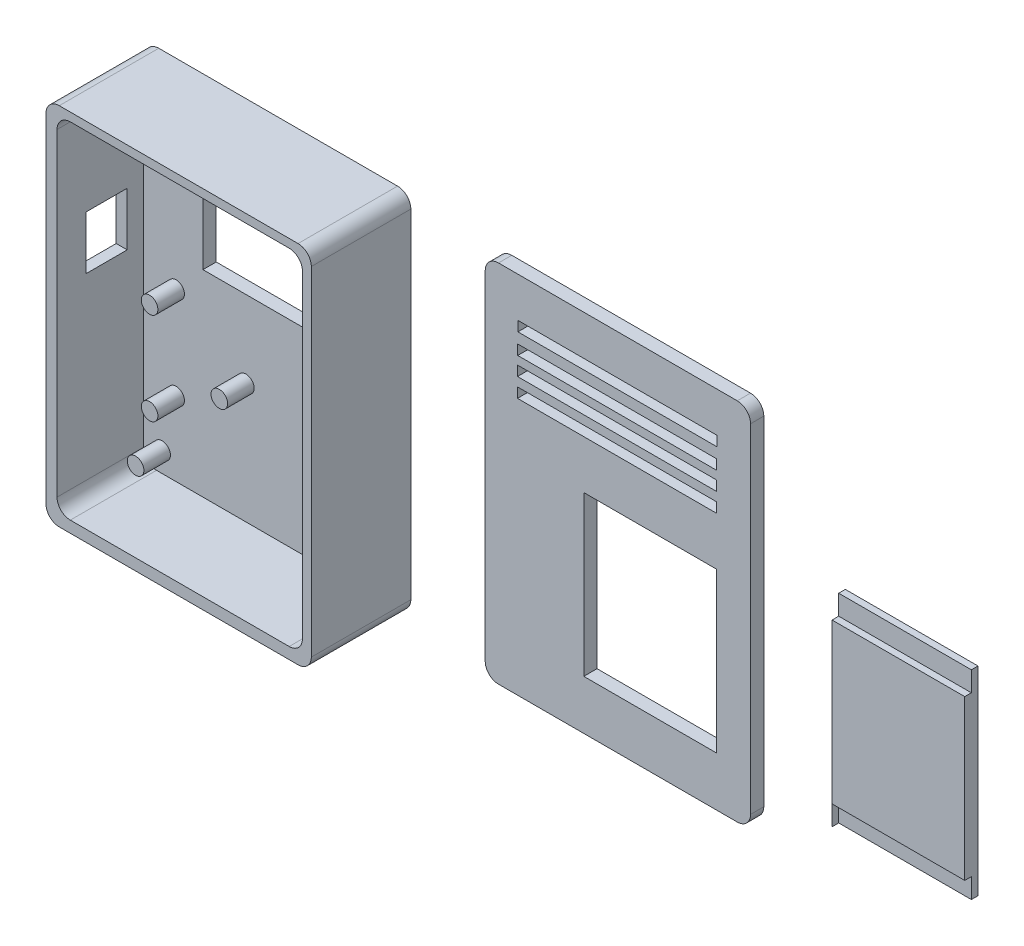
SolidWorks part; units mm, degrees
ref_plane "Front Plane" through (0, 0, 0) normal (0, 0, 1) x (1, 0, 0)
ref_plane "Top Plane" through (0, 0, 0) normal (0, 1, 0) x (1, 0, 0)
ref_plane "Right Plane" through (0, 0, 0) normal (1, 0, 0) x (0, 0, -1)
sketch "Sketch1" plane through (0, 0, 0) normal (0, 0, 1) x (1, 0, 0)
  line L1 (20.9745, 66.7151) -> (92.9745, 66.7151)
  line L2 (16.9745, 62.7151) -> (16.9745, -39.2849)
  line L3 (20.9745, -43.2849) -> (92.9745, -43.2849)
  line L4 (96.9745, 62.7151) -> (96.9745, -39.2849)
  line L12 (-85.4555, 67.5638) -> (-13.4555, 67.5638)
  line L13 (-89.4555, 63.5638) -> (-89.4555, -38.4362)
  line L14 (-85.4555, -42.4362) -> (-13.4555, -42.4362)
  line L15 (-9.4555, 63.5638) -> (-9.4555, -38.4362)
  arc A0 (16.9745, -39.2849) -> (20.9745, -43.2849) centre (20.9745, -39.2849) ccw
  arc A1 (92.9745, -43.2849) -> (96.9745, -39.2849) centre (92.9745, -39.2849) ccw
  arc A2 (92.9745, 66.7151) -> (96.9745, 62.7151) centre (92.9745, 62.7151) cw
  arc A3 (20.9745, 66.7151) -> (16.9745, 62.7151) centre (20.9745, 62.7151) ccw
  arc A4 (-13.4555, -42.4362) -> (-9.4555, -38.4362) centre (-13.4555, -38.4362) ccw
  arc A5 (-89.4555, -38.4362) -> (-85.4555, -42.4362) centre (-85.4555, -38.4362) ccw
  arc A6 (-13.4555, 67.5638) -> (-9.4555, 63.5638) centre (-13.4555, 63.5638) cw
  arc A7 (-85.4555, 67.5638) -> (-89.4555, 63.5638) centre (-85.4555, 63.5638) ccw
  dimension "D1" = 4
extrude "Boss-Extrude1" add sketch "Sketch1" along normal blind 30 contours L12 A6 L15 A4 L14 A5 L13 A7 | L2 A0 L3 A1 L4 A2 L1 A3
sketch "Sketch2" plane through (0, 0, 30) normal (0, 0, 1) x (1, 0, 0)
  line L13 (-68.1362, 54.108) -> (-32.6362, 54.108)
  line L14 (-68.1362, 54.108) -> (-68.1362, 20.408)
  line L15 (-68.1362, 20.408) -> (-32.6362, 20.408)
  line L16 (-32.6362, 54.108) -> (-32.6362, 20.408)
  dimension "D1" = 35.5
  dimension "D2" = 33.7
sketch "Sketch3" plane through (0, 0, 30) normal (0, 0, 1) x (1, 0, 0)
extrude "Cut-Extrude1" cut sketch "Sketch2" against normal blind 30 and the other way blind 30
sketch "Sketch4" plane through (0, 0, 30) normal (0, 0, 1) x (1, 0, 0)
  line L0 (23.9116, 63.8978) -> (89.9116, 63.8978)
  line L1 (-82.1324, 65.0073) -> (-16.1324, 65.0073)
  line L2 (-86.1324, 61.0073) -> (-86.1324, -34.9927)
  line L3 (-82.1324, -38.9927) -> (-16.1324, -38.9927)
  line L4 (-12.1324, 61.0073) -> (-12.1324, -34.9927)
  line L5 (19.9116, 59.8978) -> (19.9116, -36.1022)
  line L6 (23.9116, -40.1022) -> (89.9116, -40.1022)
  line L7 (93.9116, 59.8978) -> (93.9116, -36.1022)
  arc A0 (89.9116, 63.8978) -> (93.9116, 59.8978) centre (89.9116, 59.8978) cw
  arc A1 (89.9116, -40.1022) -> (93.9116, -36.1022) centre (89.9116, -36.1022) ccw
  arc A2 (23.9116, 63.8978) -> (19.9116, 59.8978) centre (23.9116, 59.8978) ccw
  arc A3 (19.9116, -36.1022) -> (23.9116, -40.1022) centre (23.9116, -36.1022) ccw
  arc A4 (-86.1324, -34.9927) -> (-82.1324, -38.9927) centre (-82.1324, -34.9927) ccw
  arc A5 (-16.1324, -38.9927) -> (-12.1324, -34.9927) centre (-16.1324, -34.9927) ccw
  arc A6 (-16.1324, 65.0073) -> (-12.1324, 61.0073) centre (-16.1324, 61.0073) cw
  arc A7 (-82.1324, 65.0073) -> (-86.1324, 61.0073) centre (-82.1324, 61.0073) ccw
  point P12 (93.9116, -40.1022)
  point P15 (19.9116, 63.8978)
  point P18 (19.9116, -40.1022)
  point P21 (-86.1324, -38.9927)
  point P26 (-12.1324, 65.0073)
  point P29 (-86.1324, 65.0073)
  dimension "D5" = 4
  dimension "D1" = 74
  dimension "D2" = 104
  dimension "D3" = 104
  dimension "D4" = 74
extrude "Cut-Extrude3" cut sketch "Sketch4" against normal blind 26
sketch "Sketch6" plane through (0, 0, 4) normal (0, 0, 1) x (1, 0, 0)
  circle A0 centre (-80.44, 58.9698) radius 2.5
  circle A1 centre (-80.44, -32.9338) radius 2.5
  circle A2 centre (-19.0808, 58.4292) radius 2.5
  circle A3 centre (-19.0808, -32.9338) radius 2.5
  circle A6 centre (-76.2183, -16.5892) radius 2.5
  circle A7 centre (-76.2183, 11.2047) radius 2.5
  circle A8 centre (-55.1947, -2.8704) radius 2.5
extrude "Boss-Extrude4" add sketch "Sketch6" along normal blind 8
sketch "Sketch7" plane through (0, 0, 0) normal (0, 0, -1) x (-1, 0, 0)
  line L1 (30.038, 15.7633) -> (70.038, 15.7633)
  line L2 (30.038, 15.7633) -> (30.038, -24.2367)
  line L3 (30.038, -24.2367) -> (70.038, -24.2367)
  line L4 (70.038, 15.7633) -> (70.038, -24.2367)
  dimension "D1" = 40
  dimension "D2" = 40
extrude "Cut-Extrude4" cut sketch "Sketch7" against normal blind 2
sketch "Sketch8" plane through (0, 0, 2) normal (0, 0, -1) x (-1, 0, 0)
  line L1 (31.3171, -6.8207) -> (34.3171, -6.8207)
  line L2 (31.3171, -6.8207) -> (31.3171, -22.8207)
  line L3 (31.3171, -22.8207) -> (34.3171, -22.8207)
  line L4 (34.3171, -6.8207) -> (34.3171, -22.8207)
  dimension "D1" = 16
  dimension "D2" = 3
extrude "Cut-Extrude6" cut sketch "Sketch8" against normal blind 10
sketch "Sketch9" plane through (0, 0, 0) normal (0, 0, -1) x (-1, 0, 0)
  circle A0 centre (20.4032, -14.9177) radius 6
extrude "Cut-Extrude7" cut sketch "Sketch9" against normal blind 10
sketch "Sketch10" plane through (-89.4555, 0, 0) normal (-1, 0, 0) x (0, 0, 1)
  line L1 (8.8325, 35.0893) -> (21.3325, 35.0893)
  line L2 (8.8325, 35.0893) -> (8.8325, 18.9893)
  line L3 (8.8325, 18.9893) -> (21.3325, 18.9893)
  line L4 (21.3325, 35.0893) -> (21.3325, 18.9893)
  dimension "D1" = 12.5
  dimension "D2" = 16.1
extrude "Cut-Extrude8" cut sketch "Sketch10" against normal blind 10
sketch "Sketch11" plane through (0, 0, 30) normal (0, 0, 1) x (1, 0, 0)
  line L1 (9.921, 71.5371) -> (105.2426, 71.5371)
  line L2 (9.921, 71.5371) -> (9.921, -48.793)
  line L3 (9.921, -48.793) -> (105.2426, -48.793)
  line L4 (105.2426, 71.5371) -> (105.2426, -48.793)
extrude "Cut-Extrude9" cut sketch "Sketch11" against normal blind 26
sketch "Sketch12" plane through (0, 0, 0) normal (0, 0, -1) x (-1, 0, 0)
  line L0 (-86.7795, 48.4571) -> (-26.7795, 48.4571)
  line L1 (-86.829, 54.6465) -> (-26.829, 54.6465)
  line L2 (-86.829, 54.6465) -> (-86.829, 51.6465)
  line L3 (-86.829, 51.6465) -> (-26.829, 51.6465)
  line L4 (-26.829, 54.6465) -> (-26.829, 51.6465)
  line L5 (-86.7795, 48.4571) -> (-86.7795, 45.4571)
  line L6 (-86.7795, 45.4571) -> (-26.7795, 45.4571)
  line L7 (-26.7795, 48.4571) -> (-26.7795, 45.4571)
  line L8 (-86.7051, 42.9232) -> (-26.7051, 42.9232)
  line L9 (-86.7051, 42.9232) -> (-86.7051, 39.9232)
  line L10 (-86.7051, 39.9232) -> (-26.7051, 39.9232)
  line L11 (-26.7051, 42.9232) -> (-26.7051, 39.9232)
  line L12 (-86.7051, 37.2186) -> (-26.7051, 37.2186)
  line L13 (-86.7051, 37.2186) -> (-86.7051, 34.2186)
  line L14 (-86.7051, 34.2186) -> (-26.7051, 34.2186)
  line L15 (-26.7051, 37.2186) -> (-26.7051, 34.2186)
extrude "Cut-Extrude10" cut sketch "Sketch12" against normal blind 10
sketch "Sketch13" plane through (0, 0, 0) normal (0, 0, -1) x (-1, 0, 0)
  line L1 (-86.6954, 19.6233) -> (-46.6954, 19.6233)
  line L2 (-86.6954, 19.6233) -> (-86.6954, -28.3767)
  line L3 (-86.6954, -28.3767) -> (-46.6954, -28.3767)
  line L4 (-46.6954, 19.6233) -> (-46.6954, -28.3767)
  dimension "D1" = 40
  dimension "D2" = 48
extrude "Cut-Extrude11" cut sketch "Sketch13" against normal blind 10
sketch "Sketch14" plane through (3.9279, 1.3405, 0) normal (0, 0, -1) x (-1, 0, 0)
  line L1 (-153.6315, 24.4255) -> (-113.6315, 24.4255)
  line L2 (-153.6315, 24.4255) -> (-153.6315, -35.5745)
  line L3 (-153.6315, -35.5745) -> (-113.6315, -35.5745)
  line L4 (-113.6315, 24.4255) -> (-113.6315, -35.5745)
  dimension "D1" = 60
  dimension "D2" = 40
extrude "Boss-Extrude5" add sketch "Sketch14" along normal blind 4 separate body
sketch "Sketch15" plane through (0, 0, 0) normal (0, 0, -1) x (-1, 0, 0)
  line L0 (-46.6954, 19.6233) -> (-86.6954, 19.6233) construction
  line L1 (-86.6998, 25.6233) -> (-46.6998, 25.6233)
  line L2 (-86.6998, 25.6233) -> (-86.6998, 19.6233)
  line L3 (-86.6998, 19.6233) -> (-46.6998, 19.6233)
  line L4 (-46.6998, 25.6233) -> (-46.6998, 19.6233)
  line L5 (-86.6807, -28.3835) -> (-46.6807, -28.3835)
  line L6 (-86.6807, -28.3835) -> (-86.6807, -34.3835)
  line L7 (-86.6807, -34.3835) -> (-46.6807, -34.3835)
  line L8 (-46.6807, -28.3835) -> (-46.6807, -34.3835)
  dimension "D1" = 6
  dimension "D2" = 40
extrude "Cut-Extrude12" cut sketch "Sketch15" against normal blind 2
sketch "Sketch16" plane through (0, 0, 0) normal (0, 0, 1) x (1, 0, 0)
  line L0 (157.5594, 25.766) -> (157.5594, -34.234) construction
  line L1 (117.5594, 25.766) -> (157.5594, 25.766)
  line L2 (117.5594, 25.766) -> (117.5594, 19.766)
  line L3 (117.5594, 19.766) -> (157.5594, 19.766)
  line L4 (157.5594, 25.766) -> (157.5594, 19.766)
  line L5 (117.56, -28.2365) -> (157.56, -28.2365)
  line L6 (117.56, -28.2365) -> (117.56, -34.2365)
  line L7 (117.56, -34.2365) -> (157.56, -34.2365)
  line L8 (157.56, -28.2365) -> (157.56, -34.2365)
  dimension "D1" = 6
extrude "Cut-Extrude16" cut sketch "Sketch16" against normal blind 2
